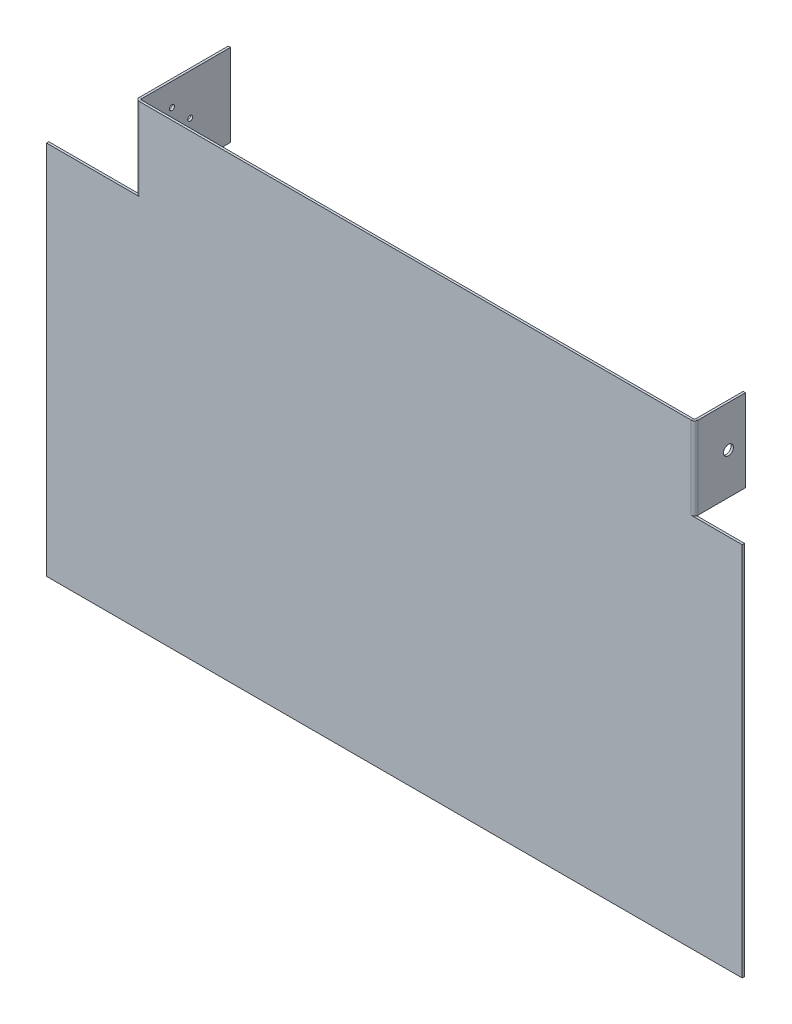
SolidWorks part; units mm, degrees
note: The reader was unsure of these and kept them because the rebuilt part matched: flange length of "Edge-Flange1", "Edge-Flange2".
ref_plane "Front Plane" through (0, 0, 0) normal (0, 0, 1) x (1, 0, 0)
ref_plane "Top Plane" through (0, 0, 0) normal (0, 1, 0) x (1, 0, 0)
ref_plane "Right Plane" through (0, 0, 0) normal (1, 0, 0) x (0, 0, -1)
sketch "Sketch1" plane through (0, 0, 0) normal (0, 0, 1) x (1, 0, 0)
  line L0 (0, 0) -> (0, 206.1243) construction
  line L1 (0, 0) -> (-276.9185, 0) construction
  line L3 (0, 0) -> (-304, 0)
  line L4 (0, 0) -> (0, 200)
  line L5 (0, 200) -> (-304, 200)
  line L6 (-304, 0) -> (-304, 200)
  dimension "D1" = 200
  dimension "D2" = 304
base flange "Base-Flange1" sketch "Sketch1" thickness 1 reverse thickness direction no parameters "D1"=2
sketch "Sketch2" plane through (0, 0, 0) normal (0, 0, 1) x (1, 0, 0)
  line L0 (-265, 200) -> (-265, 164)
  line L1 (0, 200) -> (-304, 200) construction
  line L2 (-265, 164) -> (-304, 164)
  line L3 (-304, 200) -> (-304, 0) construction
  line L4 (0, 200) -> (-304, 200) construction
  line L5 (-304, 164) -> (-304, 200)
  line L6 (-304, 200) -> (-265, 200)
  dimension "D1" = 39
  dimension "D2" = 36
extrude "Cut-Extrude1" cut sketch "Sketch2" against normal blind 10 normal cut yes
edge flange "Edge-Flange1" sketch "Sketch7" flange angle 90 flange length 40.429 flange position material inside bend radius 0.5 thickness 1 relief none parameters "D6"=10
sketch "Sketch7" plane through (-265, 0, -1) normal (1, 0, 0) x (0, -1, 0)
  line L1 (-164, 0) -> (-200, 0) construction
  line L2 (-200, 0) -> (-200, 39.429)
  line L3 (-200, 39.429) -> (-164, 39.429)
  line L4 (-164, 39.429) -> (-164, 0)
  line L5 (-164, 0) -> (-200, 0)
bend "EdgeBend1" bend radius 0.5 bend angle 90 parameters "D5"=1
sketch "Sketch9" plane through (-264, 0, 0) normal (1, 0, 0) x (0, 0, -1)
  line L0 (1, 200) -> (1, 164) construction
  line L2 (40.429, 200) -> (1.5, 200) construction
  circle A0 centre (22.8, 182) radius 1.1
  circle A1 centre (14.8, 190) radius 1.1
  circle A2 centre (14.8, 174) radius 1.1
  circle A3 centre (6.8, 182) radius 1.1
  circle A4 centre (14.8, 182) radius 3
  point P15 (14.8, 182)
  dimension "D1" = 4
  dimension "D4" = 2.2
  dimension "D2" = 6
  dimension "D3" = 13.8
  dimension "D6" = 10
extrude "Cut-Extrude2" cut sketch "Sketch9" against normal blind 10 normal cut yes
ref_plane "Plane1" through (-152, 0, 0) normal (-1, 0, 0) x (0, 0, 1)
sketch "Sketch18" plane through (0, 0, 0) normal (0, 0, 1) x (1, 0, 0)
  line L0 (0, 200) -> (-263.5, 200) construction
  line L1 (-20.8, 200) -> (0, 200)
  line L2 (-20.8, 200) -> (-20.8, 164)
  line L3 (-20.8, 164) -> (0, 164)
  line L4 (0, 200) -> (0, 164)
  line L5 (0, 0) -> (0, 200) construction
  dimension "D1" = 36
  dimension "D2" = 20.8
extrude "Cut-Extrude4" cut sketch "Sketch18" against normal up to next normal cut yes
edge flange "Edge-Flange2" sketch "Sketch21" flange angle 90 flange length 22.2292 flange position material inside bend radius 0.5 thickness 1 relief none parameters "D6"=10
sketch "Sketch21" plane through (-20.8, 0, -1) normal (1, 0, 0) x (0, -1, 0)
  line L0 (-164, 0) -> (-200, 0) construction
  line L1 (-164, 0) -> (-200, 0)
  line L2 (-200, 0) -> (-200, 21.2292)
  line L3 (-200, 21.2292) -> (-164, 21.2292)
  line L4 (-164, 21.2292) -> (-164, 0)
bend "EdgeBend2" bend radius 0.5 bend angle 90 parameters "D5"=2
hole_wizard "M4 Clearance Hole2" positions "Sketch23" profile "Sketch22" hole size "M4" standard "ANSI Metric" end condition up to next
sketch "Sketch23" plane through (-21.8, 0, 0) normal (-1, 0, 0) x (0, 0, 1)
  line L0 (-1, 164) -> (-1, 200) construction
  line L1 (-22.2292, 200) -> (-1.5, 200) construction
  point P0 (-14.8, 182)
  dimension "D1" = 13.8
  dimension "D2" = 18
sketch "Sketch22" plane through (-21.8, 182, -14.8) normal (0, 1, 0) x (0, 0, 1)
  line L0 (0, 0) -> (0, 1)
  line L1 (0, 1) -> (2.15, 1)
  line L2 (2.15, 1) -> (2.15, 0)
  line L5 (2.15, 0) -> (0, 0)
  line L11 (0, -6.35) -> (0, 107.95) construction
  dimension "Thru Hole Dia." = 4.3
  dimension "Thru Hole Depth" = 1
sketch "Bend-Lines1" [suppressed] plane through (0, 0, 0) normal (0, 1, 0) x (1, 0, 0)
sketch "Bounding-Box1" [suppressed] plane through (0, 0, 0) normal (0, 1, 0) x (1, 0, 0)
sheet metal parameters "Sheet-Metal2" thickness 1 parameters "D1"=2
flat pattern "Flat-Pattern2" [suppressed]
sketch "Bend-Lines2" plane through (0, 0, 0) normal (0, 1, 0) x (1, 0, 0)
sketch3d "Bounding-Box2" [suppressed]
  line L0 (304, 0, 0) -> (0, 0, 0) construction
  line L1 (304, 200, 0) -> (0, 200, 0) construction
  line L2 (304, 0, 0) -> (304, 200, 0) construction
  line L3 (0, 0, 0) -> (0, 200, 0) construction
sheet metal parameters "Sheet-Metal3" thickness 1 parameters "D1"=2
flat pattern "Flat-Pattern2"
sketch "Bend-Lines2" plane through (0, 0, 0) normal (0, 1, 0) x (1, 0, 0)
sketch3d "Bounding-Box2" [suppressed]
  line L0 (-304, 0, 0) -> (0, 0, 0) construction
  line L1 (-304, 200, 0) -> (0, 200, 0) construction
  line L2 (-304, 0, 0) -> (-304, 200, 0) construction
  line L3 (0, 0, 0) -> (0, 200, 0) construction
sheet metal parameters "Sheet-Metal4" thickness 1 parameters "D1"=2
flat pattern "Flat-Pattern2"
sketch "Bend-Lines2" plane through (0, 0, 0) normal (0, 0, 1) x (1, 0, 0)
  line L0 (-264.2854, 164) -> (-264.2854, 200) construction
  line L1 (-264.2854, 164) -> (-264.2854, 200) construction
sketch3d "Bounding-Box2" [suppressed]
  line L0 (-303.9998, 200, 0) -> (0, 200, 0) construction
  line L1 (-303.9998, 0, 0) -> (0, 0, 0) construction
  line L2 (-303.9998, 200, 0) -> (-303.9998, 0, 0) construction
  line L3 (0, 200, 0) -> (0, 0, 0) construction
bend of the flat pattern "Flatten-<EdgeBend1>1"
sheet metal parameters "Sheet-Metal5" thickness 1 parameters "D1"=2
flat pattern "Flat-Pattern2"
sketch "Bend-Lines2" plane through (0, 0, 0) normal (0, 0, 1) x (1, 0, 0)
  line L0 (-264.2854, 164) -> (-264.2854, 200) construction
  line L1 (-264.2854, 164) -> (-264.2854, 200) construction
sketch3d "Bounding-Box2" [suppressed]
  line L0 (-303.9998, 200, 0) -> (0, 200, 0) construction
  line L1 (-303.9998, 0, 0) -> (0, 0, 0) construction
  line L2 (-303.9998, 200, 0) -> (-303.9998, 0, 0) construction
  line L3 (0, 200, 0) -> (0, 0, 0) construction
bend of the flat pattern "Flatten-<EdgeBend1>1"
sheet metal parameters "Sheet-Metal10" thickness 1 parameters "D1"=2
flat pattern "Flat-Pattern2"
sketch "Bend-Lines2" plane through (0, 0, 0) normal (0, 0, 1) x (1, 0, 0)
  line L0 (-264.2854, 164) -> (-264.2854, 200) construction
  line L1 (-264.2854, 164) -> (-264.2854, 200) construction
sketch3d "Bounding-Box2" [suppressed]
  line L0 (-303.9989, 200.0016, 0) -> (0.0001, 199.9999, 0) construction
  line L1 (-304, 0.0017, 0) -> (-0.001, 0, 0) construction
  line L2 (-303.9989, 200.0016, 0) -> (-304, 0.0017, 0) construction
  line L3 (0.0001, 199.9999, 0) -> (-0.001, 0, 0) construction
bend of the flat pattern "Flatten-<EdgeBend1>1"
sheet metal parameters "Sheet-Metal11" thickness 1 parameters "D1"=2
flat pattern "Flat-Pattern2"
sketch "Bend-Lines2" plane through (0, 0, 0) normal (0, 0, 1) x (1, 0, 0)
  line L0 (-264.2854, 164) -> (-264.2854, 200) construction
  line L1 (-264.2854, 164) -> (-264.2854, 200) construction
  line L2 (-21.5146, 200) -> (-21.5146, 175) construction
  line L3 (-21.5146, 200) -> (-21.5146, 175) construction
sketch3d "Bounding-Box2" [suppressed]
  line L0 (-303.9994, 200.0009, 0) -> (11.7708, 200, 0) construction
  line L1 (-304, 0.0009, 0) -> (11.7702, 0, 0) construction
  line L2 (-303.9994, 200.0009, 0) -> (-304, 0.0009, 0) construction
  line L3 (11.7708, 200, 0) -> (11.7702, 0, 0) construction
bend of the flat pattern "Flatten-<EdgeBend1>1"
bend of the flat pattern "Flatten-<EdgeBend2>1"
sheet metal parameters "Sheet-Metal12" thickness 1 parameters "D1"=2
flat pattern "Flat-Pattern2"
sketch "Bend-Lines2" plane through (0, 0, 0) normal (0, 0, 1) x (1, 0, 0)
  line L0 (-264.2854, 164) -> (-264.2854, 200) construction
  line L1 (-264.2854, 164) -> (-264.2854, 200) construction
  line L2 (-21.5146, 200) -> (-21.5146, 164) construction
  line L3 (-21.5146, 200) -> (-21.5146, 164) construction
sketch3d "Bounding-Box2" [suppressed]
  line L0 (-303.9998, 200, 0) -> (0, 200, 0) construction
  line L1 (-303.9998, 0, 0) -> (0, 0, 0) construction
  line L2 (-303.9998, 200, 0) -> (-303.9998, 0, 0) construction
  line L3 (0, 200, 0) -> (0, 0, 0) construction
bend of the flat pattern "Flatten-<EdgeBend1>1"
bend of the flat pattern "Flatten-<EdgeBend2>1"
equation "\"length_edge_flange\" = 33.11mm"
equation "\"distance_fente_rampe\" = 158.61mm"
equation "\"distance_interieur\" = 300mm"
equation "\"longeur_interieur\"= 274.9mm"
equation "\"distance_trou\" = 28.82mm"
equation "\"hauteur_conteneur\"= 200mm"
